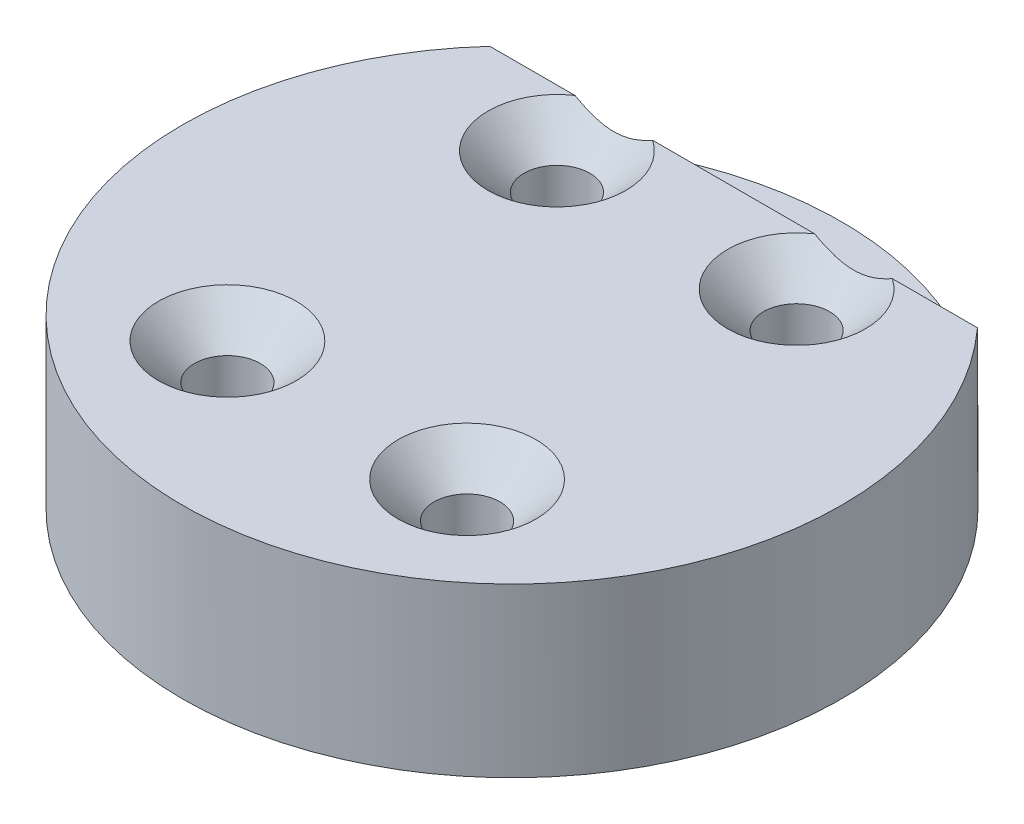
SolidWorks part; units mm, degrees
ref_plane "Front Plane" through (0, 0, 0) normal (0, 0, 1) x (1, 0, 0)
ref_plane "Top Plane" through (0, 0, 0) normal (0, 1, 0) x (1, 0, 0)
ref_plane "Right Plane" through (0, 0, 0) normal (1, 0, 0) x (0, 0, -1)
sketch "Sketch1" plane through (0, 0, 0) normal (0, 1, 0) x (1, 0, 0)
  line L0 (0, 0) -> (0, 68.5524) construction
  line L1 (0, 52.4907) -> (0, -49.3242) construction
  line L2 (10, -13.75) -> (10, 13.75)
  line L3 (10, -13.75) -> (-10, -13.75)
  line L4 (10, 13.75) -> (-10, 13.75)
  line L5 (-10, -13.75) -> (-10, 13.75)
  line L6 (10, -13.75) -> (-10, 13.75) construction
  line L7 (10, 13.75) -> (-10, -13.75) construction
  circle A0 centre (0, 0) radius 27.5
  circle A1 centre (-10, 13.75) radius 2.75
  circle A2 centre (10, 13.75) radius 2.75
  circle A3 centre (10, -13.75) radius 2.75
  circle A4 centre (-10, -13.75) radius 2.75
  dimension "D1" = 55
  dimension "D5" = 5.5
  dimension "D3" = 27.5
  dimension "D4" = 20
extrude "Boss-Extrude1" add sketch "Sketch1" along normal blind 14 contours A0 A4 L5 A1 L4 A2 L2 A3 L3 | A4 L3 A3 L2 A2 L4 A1 L5 region at (0, 0, 0) region at (-26.7222, 0, 0)
chamfer "Chamfer1" distance 3 angle 45 4 edges at (-10, 14, 16.5) (10, 14, 16.5) (10, 14, -11) (-10, 14, -11)
sketch "Sketch2" plane through (0, 14, 0) normal (0, -1, 0) x (1, 0, 0)
  line L0 (0, 15.5283) -> (0, -9.3063) construction
  line L1 (-27.5, -18.5) -> (-27.5, 0) construction
  line L2 (-27.5, -18.5) -> (27.5, -18.5)
  line L3 (-27.5, -18.5) -> (-27.5, -27.5)
  line L4 (-27.5, -27.5) -> (27.5, -27.5)
  line L5 (27.5, -18.5) -> (27.5, -27.5)
  line L6 (-27.5, -18.5) -> (27.5, -27.5) construction
  line L7 (-27.5, -27.5) -> (27.5, -18.5) construction
  line L8 (-27.5, 0) -> (27.5, 0) construction
  circle A0 centre (0, 0) radius 27.5 construction
  circle A1 centre (0, 0) radius 27.5 construction
  point P1 (0, -23)
  dimension "D1" = 9
extrude "Cut-Extrude1" cut sketch "Sketch2" along normal blind 7
equation "\"LOGO_SIZE\"= 40"
equation "\"SECTION_SIZE\"= \"LOGO_SIZE\" / 6"
